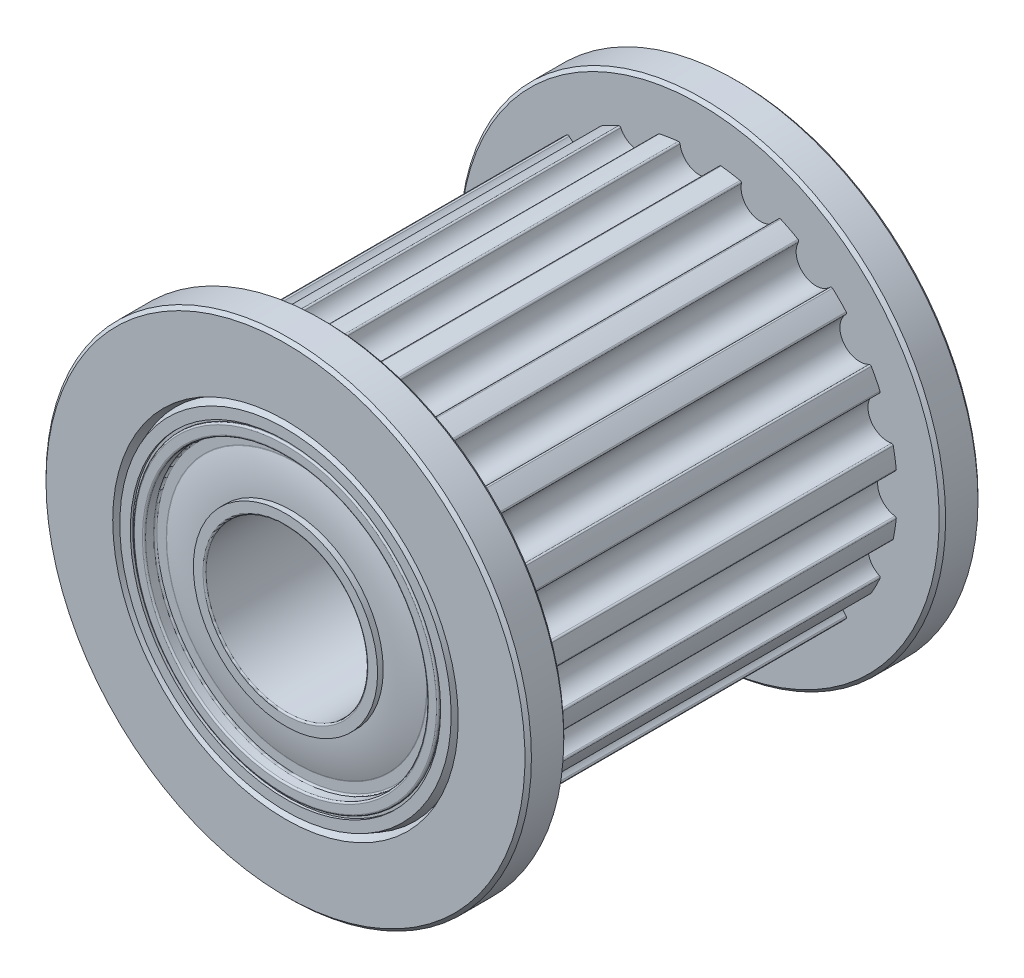
SolidWorks part; units mm, degrees
ref_plane "Front" through (0, 0, 0) normal (0, 0, 1) x (1, 0, 0)
ref_plane "Top" through (0, 0, 0) normal (0, 1, 0) x (1, 0, 0)
ref_plane "Right" through (0, 0, 0) normal (1, 0, 0) x (0, 0, -1)
sketch "Sketch1" plane through (0, 0, 0) normal (1, 0, 0) x (0, 0, -1)
  line L0 (-7, 0) -> (7, 0) construction
  line L1 (7, 7.5) -> (7, -7.5) construction
  line L2 (7, 7.5) -> (5.8, 7.5) construction
  line L3 (7, 2.5) -> (7, -2.5) construction
  line L4 (7, 6.11) -> (7, -6.11) construction
  line L5 (4.5, 0) -> (-4.5, 0) construction
  line L6 (5.8, 7.5) -> (5.8, 6.11) construction
  dimension "Width" = 14
  dimension "OD" = 15
  dimension "D3" = 1.2
  dimension "ID" = 5
  dimension "Diameter" = 12.22
  dimension "Max Belt Width" = 9
  dimension "Groove Depth" = 1.39
sketch "Sketch2" plane through (0, 0, 0) normal (1, 0, 0) x (0, 0, -1)
  line L0 (7, 2.5) -> (0, 2.5)
  line L1 (7, 2.5) -> (7, 2.8475)
  line L2 (7, 7.5) -> (7, -7.5) construction
  line L3 (7, 2.8475) -> (6.6525, 2.8475) construction
  line L4 (6.8263, 4.3725) -> (6.8263, 2.8475) construction
  line L5 (7, 4.72) -> (0, 4.72)
  line L6 (6.6525, 4.025) -> (6.6525, 4.3725)
  line L7 (7, 4.72) -> (7, 4.3725)
  line L8 (7, 4.3725) -> (6.6525, 4.3725)
  line L9 (6.6525, 4.3725) -> (6.6525, 2.8475) construction
  line L10 (0, 4.72) -> (0, 2.5)
  line L11 (6.8263, 2.8475) -> (7, 2.8475)
  arc A0 (6.6525, 4.025) -> (6.8263, 2.8475) centre (2.7494, 2.8475) cw
  dimension "D1" = 1.39
  dimension "D2" = 0.3475
revolve "Revolve1" add sketch "Sketch2" angle 360 about L0
mirror "Mirror1" about plane through (0, 0, 0) normal (0, 0, 1) of bodies 108
sketch "Sketch3" plane through (0, 0, 0) normal (1, 0, 0) x (0, 0, -1)
  line L0 (5.8, 7.5) -> (7, 7.5)
  line L1 (7, 7.5) -> (7, 5.3384)
  line L2 (7, 7.5) -> (7, -7.5) construction
  line L3 (7, 5.3384) -> (6.7, 5.2292)
  line L4 (6.7, 5.2292) -> (7, 5.12)
  line L5 (7, 5.12) -> (7, 4.795)
  line L6 (6.925, 4.72) -> (6.925, 4.795)
  line L7 (7, 4.72) -> (-7, 4.72) construction
  line L8 (6.925, 4.795) -> (7, 4.795)
  line L9 (5.8, 7.5) -> (5.8, 6.11)
  line L10 (5.8, 6.11) -> (-5.8, 6.11)
  line L11 (0, 6.11) -> (0, 4.72) construction
  line L12 (-6.925, 4.72) -> (6.925, 4.72)
  line L13 (-5.8, 7.5) -> (-5.8, 6.11)
  line L14 (-6.925, 4.795) -> (-7, 4.795)
  line L15 (-6.925, 4.72) -> (-6.925, 4.795)
  line L16 (-7, 5.12) -> (-7, 4.795)
  line L17 (-6.7, 5.2292) -> (-7, 5.12)
  line L18 (-7, 5.3384) -> (-6.7, 5.2292)
  line L19 (-7, 7.5) -> (-7, 5.3384)
  line L20 (-5.8, 7.5) -> (-7, 7.5)
  line L21 (6.7, 5.2292) -> (7, 5.2292) construction
  line L22 (6.85, 5.2292) -> (6.85, 4.72) construction
  dimension "D1" = 40
  dimension "D2" = 0.3
  dimension "D3" = 0.075
  dimension "D4" = 0.4
revolve "Revolve2" add sketch "Sketch3" angle 360 about L0
sketch "Sketch4" plane through (0, 0, 0) normal (0, 0, 1) x (1, 0, 0)
  line L0 (-0.611, 6.11) -> (0.611, 6.11)
  line L1 (-0.611, 6.11) -> (-0.611, 5.554) construction
  line L2 (-0.611, 5.554) -> (0.611, 5.554) construction
  line L3 (0.611, 5.554) -> (0.611, 6.11) construction
  line L4 (0, 6.11) -> (0, 5.554) construction
  arc A0 (0.611, 6.11) -> (-0.611, 6.11) centre (0, 6.11) cw
  dimension "D1" = 0.556
  dimension "D3" = 1.222
extrude "Cut-Extrude1" cut sketch "Sketch4" against normal up to surface and the other way up to surface up to face at (6.11, 0, -5.8) other way up to face at (7.5, 0, 5.8)
fillet "Fillet1" radius 0.05 2 edges at (0.6102, 6.0795, 0) (-0.6102, 6.0795, 0)
pattern_circular "CirPattern3" count 20 over 360 about axis through (0, 0, -5.8) along (0, 0, 1) of "Cut-Extrude1", "Fillet1"
chamfer "Chamfer1" distance 0.1 angle 45 4 edges at (7.5, 0, -7) (7.5, 0, -5.8) (7.5, 0, 5.8) (7.5, 0, 7)
fillet "Fillet2" radius 0.05 10 edges at (4.025, 0, 6.6525) (4.3725, 0, 6.6525) (4.72, 0, 7) (4.3725, 0, 7) (2.5, 0, 7) (2.5, 0, -7) (4.72, 0, -7) (4.025, 0, -6.6525) (4.3725, 0, -7) (2.8475, 0, -7)
combine bodies "Combine1" operation type add bodies to combine 113 109
ref_axis "Center Axis 1" through (0, 0, -6.95) along (0, 0, 1)
ref_plane "Contact Plane 1" through (0, 0, -4.5) normal (0, 0, 1) x (1, 0, 0)
ref_plane "Contact Plane 2" through (0, 0, 4.5) normal (0, 0, 1) x (1, 0, 0)
equation "\"D1@Sketch4\"=\"Groove Depth@Sketch1\"/2.5"
equation "\"D3@Sketch4\"=\"Diameter@Sketch1\"/10"
equation "\"D2@Sketch3\"=\"D3@Sketch1\"/4"
equation "\"D1@Sketch2\"=(\"OD@Sketch1\"-\"Diameter@Sketch1\")/2"
equation "\"D2@Sketch2\"=\"D1@Sketch2\"/4"
equation "\"D3@Sketch3\"=\"D2@Sketch3\"/4"
equation "\"D4@Sketch3\"=\"D3@Sketch1\"/3"
